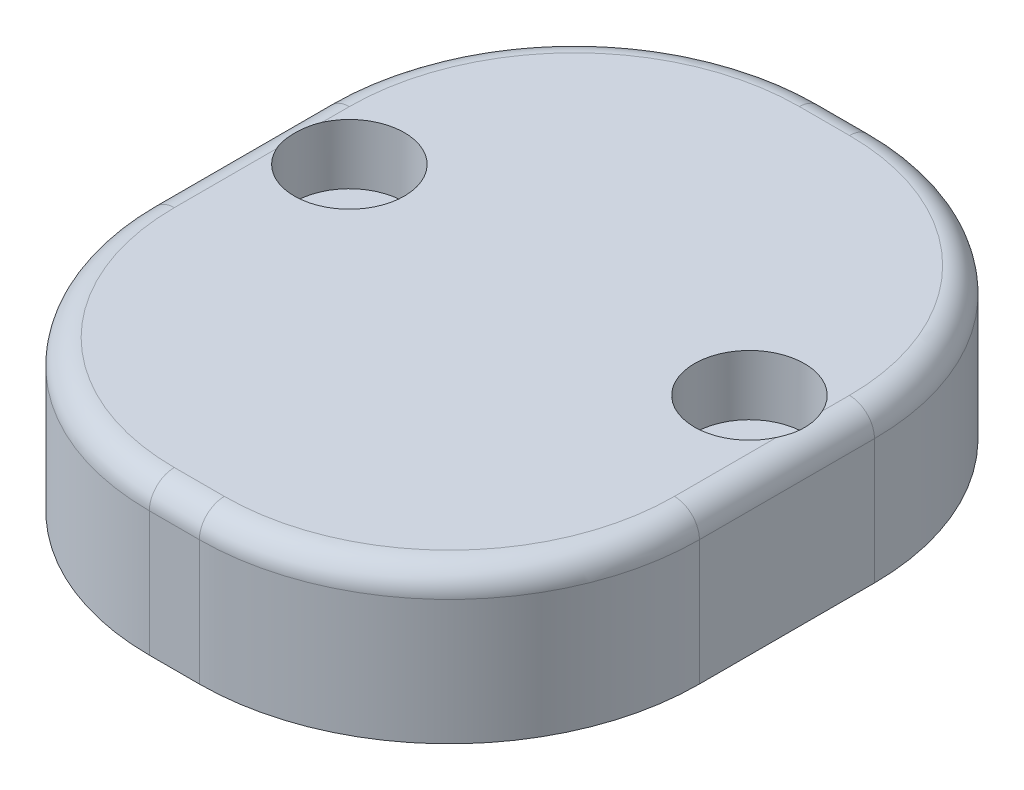
SolidWorks part; units mm, degrees
ref_plane "Plan de face" through (0, 0, 0) normal (0, 0, 1) x (1, 0, 0)
ref_plane "Plan de dessus" through (0, 0, 0) normal (0, 1, 0) x (1, 0, 0)
ref_plane "Plan de droite" through (0, 0, 0) normal (1, 0, 0) x (0, 0, -1)
sketch "Esquisse1" plane through (0, 0, 0) normal (0, 0, 1) x (1, 0, 0)
  line L1 (0, 0) -> (22, 0)
  line L2 (0, 0) -> (0, 6)
  line L3 (0, 6) -> (22, 6)
  line L4 (22, 0) -> (22, 6)
  arc A0 (6, 0) -> (16, 0) centre (11, 0) cw
  dimension "D3" = 5
  dimension "D1" = 6
  dimension "D2" = 22
  dimension "D4" = 11
extrude "Boss.-Extru.1" add sketch "Esquisse1" along normal blind 22 contours L1 A0 L4 L3 L2 region at (0.228, 3, 0)
sketch "Esquisse2" plane through (0, 0, 22) normal (0, 0, 1) x (1, 0, 0)
  line L1 (0, 0) -> (22, 0)
  line L2 (0, 0) -> (0, 6)
  line L3 (0, 6) -> (22, 6)
  line L4 (22, 0) -> (22, 6)
extrude "Boss.-Extru.2" add sketch "Esquisse2" along normal blind 5
hole_wizard "Chambrage pour vis à tête hexagonale M21" positions "Esquisse3" profile "Esquisse4" counterbore size "M2" standard "ISO" end condition through all
sketch "Esquisse3" plane through (0, 6, 0) normal (0, 1, 0) x (1, 0, 0)
  line L0 (11, -31.2926) -> (11, 8.1795) construction
  line L2 (0, -27) -> (0, 0) construction
  line L4 (0, 0) -> (22, 0) construction
  point P0 (19, -12)
  point P2 (3, -12)
  dimension "D1" = 16
  dimension "D2" = 11
  dimension "D3" = 8
  dimension "D4" = 12
  dimension "D5" = 12
sketch "Esquisse4" plane through (19, 6, 12) normal (1, 0, 0) x (0, 0, 1)
  line L0 (0, 0) -> (0, 6)
  line L1 (0, 6) -> (1.2, 6)
  line L3 (1.2, 6) -> (1.2, 2.4)
  line L4 (1.2, 2.4) -> (2.2, 2.4)
  line L5 (2.2, 2.4) -> (2.2, 0)
  line L7 (2.2, 0) -> (0, 0)
  line L11 (0, -6.35) -> (0, 107.95) construction
  dimension "Diamètre du perçage jusqu'au prochain" = 2.4
  dimension "Profondeur du perçage jusqu'au prochain" = 6
  dimension "Diamètre du chambrage" = 4.4
  dimension "Profondeur du chambrage" = 2.4
fillet "Congé1" radius 10 4 edges at (0, 3, 0) (0, 3, 27) (22, 3, 0) (22, 3, 27)
fillet "Congé2" radius 1 8 edges at (22, 6, 13.5) (19.0711, 6, 2.9289) (11, 6, 0) (2.9289, 6, 2.9289) (0, 6, 13.5) (2.9289, 6, 24.0711) (11, 6, 27) (19.0711, 6, 24.0711)
